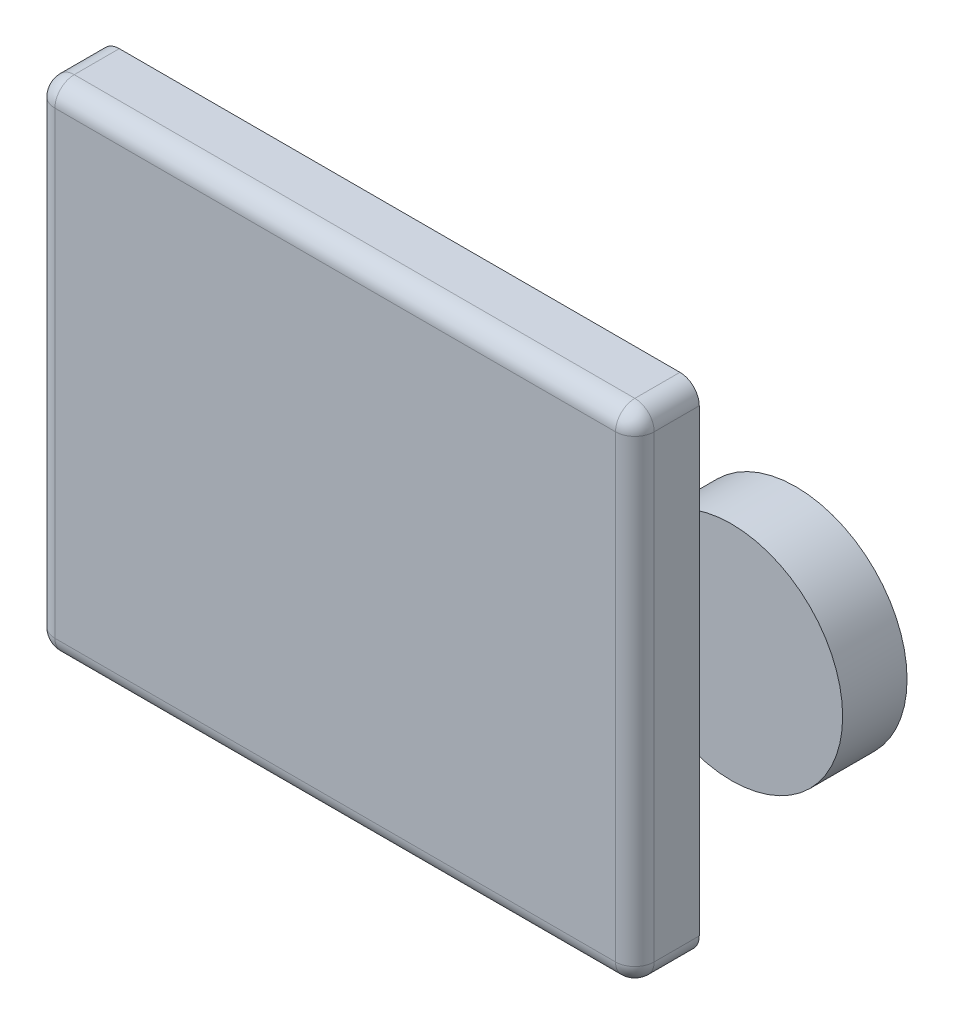
SolidWorks part; units mm, degrees
ref_plane "Спереди" through (0, 0, 0) normal (0, 0, 1) x (1, 0, 0)
ref_plane "Сверху" through (0, 0, 0) normal (0, 1, 0) x (1, 0, 0)
ref_plane "Справа" through (0, 0, 0) normal (1, 0, 0) x (0, 0, -1)
sketch "Эскиз1_fr" plane through (0, 0, 0) normal (0, 0, 1) x (1, 0, 0)
  line L1 (-48.994, 38.0205) -> (44.0482, 38.0205)
  line L2 (-48.994, 38.0205) -> (-48.994, -39.257)
  line L3 (-48.994, -39.257) -> (44.0482, -39.257)
  line L4 (44.0482, 38.0205) -> (44.0482, -39.257)
extrude "Бобышка-Вытянуть1" add sketch "Эскиз1_fr" along normal blind 10
ref_plane "Плоскость4" through (0, 0, -5) normal (0, 0, 1) x (1, 0, 0)
sketch "Эскиз5" plane through (0, 0, -5) normal (0, 0, 1) x (1, 0, 0)
  line L0 (44.0482, -39.257) -> (44.0482, 38.0205) construction
  circle A0 centre (44.0482, -0.6182) radius 17.2618
extrude "Бобышка-Вытянуть2" add sketch "Эскиз5" against normal blind 10 separate body
fillet "Скругление1" radius 3 4 edges at (-2.4729, 38.0205, 10) (-48.994, -0.6182, 10) (-2.4729, -39.257, 10) (44.0482, -0.6182, 10)
fillet "Скругление2" radius 3 2 edges at (43.1695, -38.3783, 9.1213) (44.0482, -39.257, 3.5)
fillet "Скругление3" radius 3 6 edges at (-48.1153, -38.3783, 9.1213) (-48.1153, 37.1419, 9.1213) (43.1695, 37.1419, 9.1213) (-48.994, -39.257, 3.5) (-48.994, 38.0205, 3.5) (44.0482, 38.0205, 3.5)
